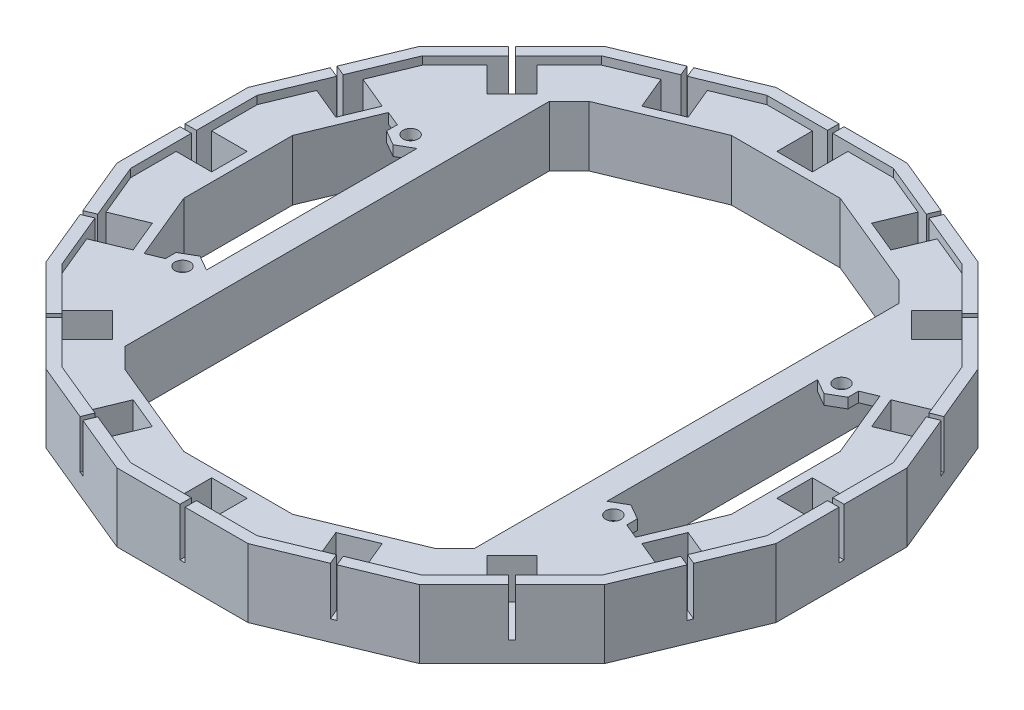
SolidWorks part; units mm, degrees
ref_plane "Front Plane" through (0, 0, 0) normal (0, 0, 1) x (1, 0, 0)
ref_plane "Top Plane" through (0, 0, 0) normal (0, 1, 0) x (1, 0, 0)
ref_plane "Right Plane" through (0, 0, 0) normal (1, 0, 0) x (0, 0, -1)
sketch "Sketch1" plane through (0, 0, 0) normal (0, 1, 0) x (1, 0, 0)
  line L19 (55.1043, 36.8195) -> (36.8195, 55.1043)
  line L20 (36.8195, 55.1043) -> (12.9293, 65)
  line L21 (12.9293, 65) -> (-12.9293, 65)
  line L22 (-12.9293, 65) -> (-36.8195, 55.1043)
  line L23 (-36.8195, 55.1043) -> (-55.1043, 36.8195)
  line L24 (-55.1043, 36.8195) -> (-65, 12.9293)
  line L25 (-65, 12.9293) -> (-65, -12.9293)
  line L26 (-65, -12.9293) -> (-55.1043, -36.8195)
  line L27 (-55.1043, -36.8195) -> (-36.8195, -55.1043)
  line L28 (-36.8195, -55.1043) -> (-12.9293, -65)
  line L29 (-12.9293, -65) -> (12.9293, -65)
  line L30 (12.9293, -65) -> (36.8195, -55.1043)
  line L31 (36.8195, -55.1043) -> (55.1043, -36.8195)
  line L32 (55.1043, -36.8195) -> (65, -12.9293)
  line L33 (65, -12.9293) -> (65, 12.9293)
  line L34 (65, 12.9293) -> (55.1043, 36.8195)
  line L35 (10.7413, 54) -> (-10.7413, 54)
  line L36 (-10.7413, 54) -> (-30.5885, 45.779)
  line L37 (-30.5885, 45.779) -> (-45.779, 30.5885)
  line L38 (-45.779, 30.5885) -> (-54, 10.7413)
  line L39 (-54, 10.7413) -> (-54, -10.7413)
  line L40 (-54, -10.7413) -> (-45.779, -30.5885)
  line L41 (-45.779, -30.5885) -> (-30.5885, -45.779)
  line L42 (-30.5885, -45.779) -> (-10.7413, -54)
  line L43 (-10.7413, -54) -> (10.7413, -54)
  line L44 (10.7413, -54) -> (30.5885, -45.779)
  line L45 (30.5885, -45.779) -> (45.779, -30.5885)
  line L46 (45.779, -30.5885) -> (54, -10.7413)
  line L47 (54, -10.7413) -> (54, 10.7413)
  line L48 (54, 10.7413) -> (45.779, 30.5885)
  line L49 (45.779, 30.5885) -> (30.5885, 45.779)
  line L50 (30.5885, 45.779) -> (10.7413, 54)
  circle A0 centre (0, 0) radius 65 construction
  circle A1 centre (0, 0) radius 54 construction
  dimension "D1" = 130
  dimension "D2" = 11
extrude "Boss-Extrude1" add sketch "Sketch1" along normal blind 13.5
sketch "Sketch2" plane through (0, 13.5, 0) normal (0, 1, 0) x (1, 0, 0)
  line L1 (35.545, 53.1969) -> (12.4818, 62.75)
  line L2 (12.4818, 62.75) -> (-12.4818, 62.75)
  line L3 (-12.4818, 62.75) -> (-35.545, 53.1969)
  line L4 (-35.545, 53.1969) -> (-53.1969, 35.545)
  line L5 (-53.1969, 35.545) -> (-62.75, 12.4818)
  line L6 (-62.75, 12.4818) -> (-62.75, -12.4818)
  line L7 (-62.75, -12.4818) -> (-53.1969, -35.545)
  line L8 (-53.1969, -35.545) -> (-35.545, -53.1969)
  line L9 (-35.545, -53.1969) -> (-12.4818, -62.75)
  line L10 (-12.4818, -62.75) -> (12.4818, -62.75)
  line L11 (12.4818, -62.75) -> (35.545, -53.1969)
  line L12 (35.545, -53.1969) -> (53.1969, -35.545)
  line L13 (53.1969, -35.545) -> (62.75, -12.4818)
  line L14 (62.75, -12.4818) -> (62.75, 12.4818)
  line L15 (62.75, 12.4818) -> (53.1969, 35.545)
  line L16 (53.1969, 35.545) -> (35.545, 53.1969)
  circle A0 centre (0, 0) radius 62.75 construction
  dimension "D1" = 125.5
extrude "Cut-Extrude1" cut sketch "Sketch2" against normal blind 1.6
sketch "Sketch3" plane through (0, 13.5, 0) normal (0, 1, 0) x (1, 0, 0)
  line L0 (12.4818, 62.75) -> (-12.4818, 62.75) construction
  line L1 (-3.5, 62.75) -> (-0.5, 62.75)
  line L2 (-3.5, 62.75) -> (-3.5, 55.75)
  line L3 (-3.5, 55.75) -> (3.5, 55.75)
  line L4 (3.5, 62.75) -> (3.5, 55.75)
  line L5 (12.9293, 65) -> (-12.9293, 65) construction
  line L7 (-0.5, 62.75) -> (-0.5, 65)
  line L8 (-0.5, 65) -> (0.5, 65)
  line L9 (0.5, 62.75) -> (0.5, 65)
  line L10 (0.5, 62.75) -> (3.5, 62.75)
  line L11 (20.7798, 59.3128) -> (23.5514, 58.1648)
  line L12 (23.5514, 58.1648) -> (24.4125, 60.2435)
  line L13 (24.4125, 60.2435) -> (25.3364, 59.8608)
  line L14 (24.4753, 57.7821) -> (25.3364, 59.8608)
  line L15 (24.4753, 57.7821) -> (27.247, 56.634)
  line L16 (27.247, 56.634) -> (24.5682, 50.1669)
  line L17 (18.101, 52.8457) -> (24.5682, 50.1669)
  line L18 (20.7798, 59.3128) -> (18.101, 52.8457)
  line L19 (41.8961, 46.8458) -> (44.0174, 44.7245)
  line L20 (44.0174, 44.7245) -> (45.6084, 46.3155)
  line L21 (45.6084, 46.3155) -> (46.3155, 45.6084)
  line L22 (44.7245, 44.0174) -> (46.3155, 45.6084)
  line L23 (44.7245, 44.0174) -> (46.8458, 41.8961)
  line L24 (46.8458, 41.8961) -> (41.8961, 36.9463)
  line L25 (36.9463, 41.8961) -> (41.8961, 36.9463)
  line L26 (41.8961, 46.8458) -> (36.9463, 41.8961)
  line L27 (56.634, 27.247) -> (57.7821, 24.4753)
  line L28 (57.7821, 24.4753) -> (59.8608, 25.3364)
  line L29 (59.8608, 25.3364) -> (60.2435, 24.4125)
  line L30 (58.1648, 23.5514) -> (60.2435, 24.4125)
  line L31 (58.1648, 23.5514) -> (59.3128, 20.7798)
  line L32 (59.3128, 20.7798) -> (52.8457, 18.101)
  line L33 (50.1669, 24.5682) -> (52.8457, 18.101)
  line L34 (56.634, 27.247) -> (50.1669, 24.5682)
  line L35 (62.75, 3.5) -> (62.75, 0.5)
  line L36 (62.75, 0.5) -> (65, 0.5)
  line L37 (65, 0.5) -> (65, -0.5)
  line L38 (62.75, -0.5) -> (65, -0.5)
  line L39 (62.75, -0.5) -> (62.75, -3.5)
  line L40 (62.75, -3.5) -> (55.75, -3.5)
  line L41 (55.75, 3.5) -> (55.75, -3.5)
  line L42 (62.75, 3.5) -> (55.75, 3.5)
  line L43 (59.3128, -20.7798) -> (58.1648, -23.5514)
  line L44 (58.1648, -23.5514) -> (60.2435, -24.4125)
  line L45 (60.2435, -24.4125) -> (59.8608, -25.3364)
  line L46 (57.7821, -24.4753) -> (59.8608, -25.3364)
  line L47 (57.7821, -24.4753) -> (56.634, -27.247)
  line L48 (56.634, -27.247) -> (50.1669, -24.5682)
  line L49 (52.8457, -18.101) -> (50.1669, -24.5682)
  line L50 (59.3128, -20.7798) -> (52.8457, -18.101)
  line L51 (46.8458, -41.8961) -> (44.7245, -44.0174)
  line L52 (44.7245, -44.0174) -> (46.3155, -45.6084)
  line L53 (46.3155, -45.6084) -> (45.6084, -46.3155)
  line L54 (44.0174, -44.7245) -> (45.6084, -46.3155)
  line L55 (44.0174, -44.7245) -> (41.8961, -46.8458)
  line L56 (41.8961, -46.8458) -> (36.9463, -41.8961)
  line L57 (41.8961, -36.9463) -> (36.9463, -41.8961)
  line L58 (46.8458, -41.8961) -> (41.8961, -36.9463)
  line L59 (27.247, -56.634) -> (24.4753, -57.7821)
  line L60 (24.4753, -57.7821) -> (25.3364, -59.8608)
  line L61 (25.3364, -59.8608) -> (24.4125, -60.2435)
  line L62 (23.5514, -58.1648) -> (24.4125, -60.2435)
  line L63 (23.5514, -58.1648) -> (20.7798, -59.3128)
  line L64 (20.7798, -59.3128) -> (18.101, -52.8457)
  line L65 (24.5682, -50.1669) -> (18.101, -52.8457)
  line L66 (27.247, -56.634) -> (24.5682, -50.1669)
  line L67 (3.5, -62.75) -> (0.5, -62.75)
  line L68 (0.5, -62.75) -> (0.5, -65)
  line L69 (0.5, -65) -> (-0.5, -65)
  line L70 (-0.5, -62.75) -> (-0.5, -65)
  line L71 (-0.5, -62.75) -> (-3.5, -62.75)
  line L72 (-3.5, -62.75) -> (-3.5, -55.75)
  line L73 (3.5, -55.75) -> (-3.5, -55.75)
  line L74 (3.5, -62.75) -> (3.5, -55.75)
  line L75 (-20.7798, -59.3128) -> (-23.5514, -58.1648)
  line L76 (-23.5514, -58.1648) -> (-24.4125, -60.2435)
  line L77 (-24.4125, -60.2435) -> (-25.3364, -59.8608)
  line L78 (-24.4753, -57.7821) -> (-25.3364, -59.8608)
  line L79 (-24.4753, -57.7821) -> (-27.247, -56.634)
  line L80 (-27.247, -56.634) -> (-24.5682, -50.1669)
  line L81 (-18.101, -52.8457) -> (-24.5682, -50.1669)
  line L82 (-20.7798, -59.3128) -> (-18.101, -52.8457)
  line L83 (-41.8961, -46.8458) -> (-44.0174, -44.7245)
  line L84 (-44.0174, -44.7245) -> (-45.6084, -46.3155)
  line L85 (-45.6084, -46.3155) -> (-46.3155, -45.6084)
  line L86 (-44.7245, -44.0174) -> (-46.3155, -45.6084)
  line L87 (-44.7245, -44.0174) -> (-46.8458, -41.8961)
  line L88 (-46.8458, -41.8961) -> (-41.8961, -36.9463)
  line L89 (-36.9463, -41.8961) -> (-41.8961, -36.9463)
  line L90 (-41.8961, -46.8458) -> (-36.9463, -41.8961)
  line L91 (-56.634, -27.247) -> (-57.7821, -24.4753)
  line L92 (-57.7821, -24.4753) -> (-59.8608, -25.3364)
  line L93 (-59.8608, -25.3364) -> (-60.2435, -24.4125)
  line L94 (-58.1648, -23.5514) -> (-60.2435, -24.4125)
  line L95 (-58.1648, -23.5514) -> (-59.3128, -20.7798)
  line L96 (-59.3128, -20.7798) -> (-52.8457, -18.101)
  line L97 (-50.1669, -24.5682) -> (-52.8457, -18.101)
  line L98 (-56.634, -27.247) -> (-50.1669, -24.5682)
  line L99 (-62.75, -3.5) -> (-62.75, -0.5)
  line L100 (-62.75, -0.5) -> (-65, -0.5)
  line L101 (-65, -0.5) -> (-65, 0.5)
  line L102 (-62.75, 0.5) -> (-65, 0.5)
  line L103 (-62.75, 0.5) -> (-62.75, 3.5)
  line L104 (-62.75, 3.5) -> (-55.75, 3.5)
  line L105 (-55.75, -3.5) -> (-55.75, 3.5)
  line L106 (-62.75, -3.5) -> (-55.75, -3.5)
  line L107 (-59.3128, 20.7798) -> (-58.1648, 23.5514)
  line L108 (-58.1648, 23.5514) -> (-60.2435, 24.4125)
  line L109 (-60.2435, 24.4125) -> (-59.8608, 25.3364)
  line L110 (-57.7821, 24.4753) -> (-59.8608, 25.3364)
  line L111 (-57.7821, 24.4753) -> (-56.634, 27.247)
  line L112 (-56.634, 27.247) -> (-50.1669, 24.5682)
  line L113 (-52.8457, 18.101) -> (-50.1669, 24.5682)
  line L114 (-59.3128, 20.7798) -> (-52.8457, 18.101)
  line L115 (-46.8458, 41.8961) -> (-44.7245, 44.0174)
  line L116 (-44.7245, 44.0174) -> (-46.3155, 45.6084)
  line L117 (-46.3155, 45.6084) -> (-45.6084, 46.3155)
  line L118 (-44.0174, 44.7245) -> (-45.6084, 46.3155)
  line L119 (-44.0174, 44.7245) -> (-41.8961, 46.8458)
  line L120 (-41.8961, 46.8458) -> (-36.9463, 41.8961)
  line L121 (-41.8961, 36.9463) -> (-36.9463, 41.8961)
  line L122 (-46.8458, 41.8961) -> (-41.8961, 36.9463)
  line L123 (-27.247, 56.634) -> (-24.4753, 57.7821)
  line L124 (-24.4753, 57.7821) -> (-25.3364, 59.8608)
  line L125 (-25.3364, 59.8608) -> (-24.4125, 60.2435)
  line L126 (-23.5514, 58.1648) -> (-24.4125, 60.2435)
  line L127 (-23.5514, 58.1648) -> (-20.7798, 59.3128)
  line L128 (-20.7798, 59.3128) -> (-18.101, 52.8457)
  line L129 (-24.5682, 50.1669) -> (-18.101, 52.8457)
  line L130 (-27.247, 56.634) -> (-24.5682, 50.1669)
  point P6 (0, 55.75)
  point P14 (0, 65)
  point P138 (0, 0)
  dimension "D1" = 7
  dimension "D2" = 1
  dimension "D4" = 55.75
  dimension "D5" = 3.5
  dimension "D3" = 16
extrude "Cut-Extrude2" cut sketch "Sketch3" against normal blind 9.5
sketch "Sketch5" plane through (0, 11.9, 0) normal (0, 1, 0) x (1, 0, 0)
  line L0 (-39.5, 24.2321) -> (-39.5, 36.8675)
  line L1 (-42.5, -22.5) -> (42.5, -22.5) construction
  line L2 (-42.5, -22.5) -> (-42.5, 22.5) construction
  line L3 (-42.5, 22.5) -> (42.5, 22.5) construction
  line L4 (42.5, -22.5) -> (42.5, 22.5) construction
  line L5 (-42.5, -22.5) -> (42.5, 22.5) construction
  line L6 (-42.5, 22.5) -> (42.5, -22.5) construction
  line L7 (-30.5885, 45.779) -> (-45.779, 30.5885) construction
  line L8 (-42.5, 19.0359) -> (-39.5, 20.7679)
  line L9 (-39.5, 20.7679) -> (-39.5, 24.2321)
  line L12 (-45.5, 24.2321) -> (-45.5, 20.7679)
  line L13 (-45.5, 20.7679) -> (-42.5, 19.0359)
  line L32 (-45.5, 24.2321) -> (-45.5, 30.8675)
  line L33 (-45.5, 30.8675) -> (-39.5, 36.8675)
  line L34 (-39.5, 24.2321) -> (-41, 25.0981) [skipped]
  line L35 (-44, 25.0981) -> (-45.5, 24.2321) [skipped]
  line L36 (-7.425, 0) -> (7.425, 0) construction
  line L37 (-45.5, -24.2321) -> (-45.5, -30.8675)
  line L38 (-45.5, -30.8675) -> (-39.5, -36.8675)
  line L39 (-39.5, -24.2321) -> (-39.5, -36.8675)
  line L40 (-39.5, -20.7679) -> (-39.5, -24.2321)
  line L41 (-42.5, -19.0359) -> (-39.5, -20.7679)
  line L42 (-45.5, -20.7679) -> (-42.5, -19.0359)
  line L43 (-45.5, -24.2321) -> (-45.5, -20.7679)
  line L44 (0, -7.425) -> (0, 7.425) construction
  line L45 (45.5, -24.2321) -> (45.5, -20.7679)
  line L46 (45.5, -20.7679) -> (42.5, -19.0359)
  line L47 (42.5, -19.0359) -> (39.5, -20.7679)
  line L48 (39.5, -20.7679) -> (39.5, -24.2321)
  line L49 (39.5, -24.2321) -> (39.5, -36.8675)
  line L50 (45.5, -30.8675) -> (39.5, -36.8675)
  line L51 (45.5, -24.2321) -> (45.5, -30.8675)
  line L52 (45.5, 24.2321) -> (45.5, 30.8675)
  line L53 (45.5, 30.8675) -> (39.5, 36.8675)
  line L54 (39.5, 24.2321) -> (39.5, 36.8675)
  line L55 (39.5, 20.7679) -> (39.5, 24.2321)
  line L56 (42.5, 19.0359) -> (39.5, 20.7679)
  line L57 (45.5, 20.7679) -> (42.5, 19.0359)
  line L58 (45.5, 24.2321) -> (45.5, 20.7679)
  circle A0 centre (-42.5, 22.5) radius 1.5
  arc A4 (-45.5, 22.5) -> (-39.5, 22.5) centre (-42.5, 22.5) ccw construction
  circle A5 centre (42.5, 22.5) radius 1.5
  circle A6 centre (42.5, -22.5) radius 1.5
  circle A7 centre (-42.5, -22.5) radius 1.5
  point P0 (0, 0)
  dimension "D3" = 3
  dimension "D4" = 6
  dimension "D1" = 85
  dimension "D2" = 45
  dimension "D5" = 12.6355
  dimension "D6" = 6.6355
extrude "Boss-Extrude2" add sketch "Sketch5" against normal blind 2
chamfer "Chamfer1" distance 8 4 edges at (45.5, 10.9, -30.8675) (45.5, 10.9, 30.8675) (-45.5, 10.9, 30.8675) (-45.5, 10.9, -30.8675)
sketch "Sketch6" plane through (0, 0, 0) normal (0, -1, 0) x (1, 0, 0)
  line L0 (-39.5, 36.8675) -> (-34.5, 41.8675)
  line L1 (-45.779, 30.5885) -> (-30.5885, 45.779) construction
  line L2 (-34.5, 41.8675) -> (-34.5, -41.8675)
  line L3 (-30.5885, -45.779) -> (-45.779, -30.5885) construction
  line L4 (-34.5, -41.8675) -> (-39.5, -36.8675)
  line L5 (-39.5, -36.8675) -> (-39.5, 36.8675)
  line L6 (39.5, 36.8675) -> (39.5, -36.8675)
  line L7 (39.5, -36.8675) -> (34.5, -41.8675)
  line L8 (45.779, -30.5885) -> (30.5885, -45.779) construction
  line L9 (34.5, -41.8675) -> (34.5, 41.8675)
  line L10 (30.5885, 45.779) -> (45.779, 30.5885) construction
  line L11 (34.5, 41.8675) -> (39.5, 36.8675)
  dimension "D1" = 5
extrude "Boss-Extrude3" add sketch "Sketch6" against normal up to surface (11.9 mm away) up to face at (0, 11.9, 0)
